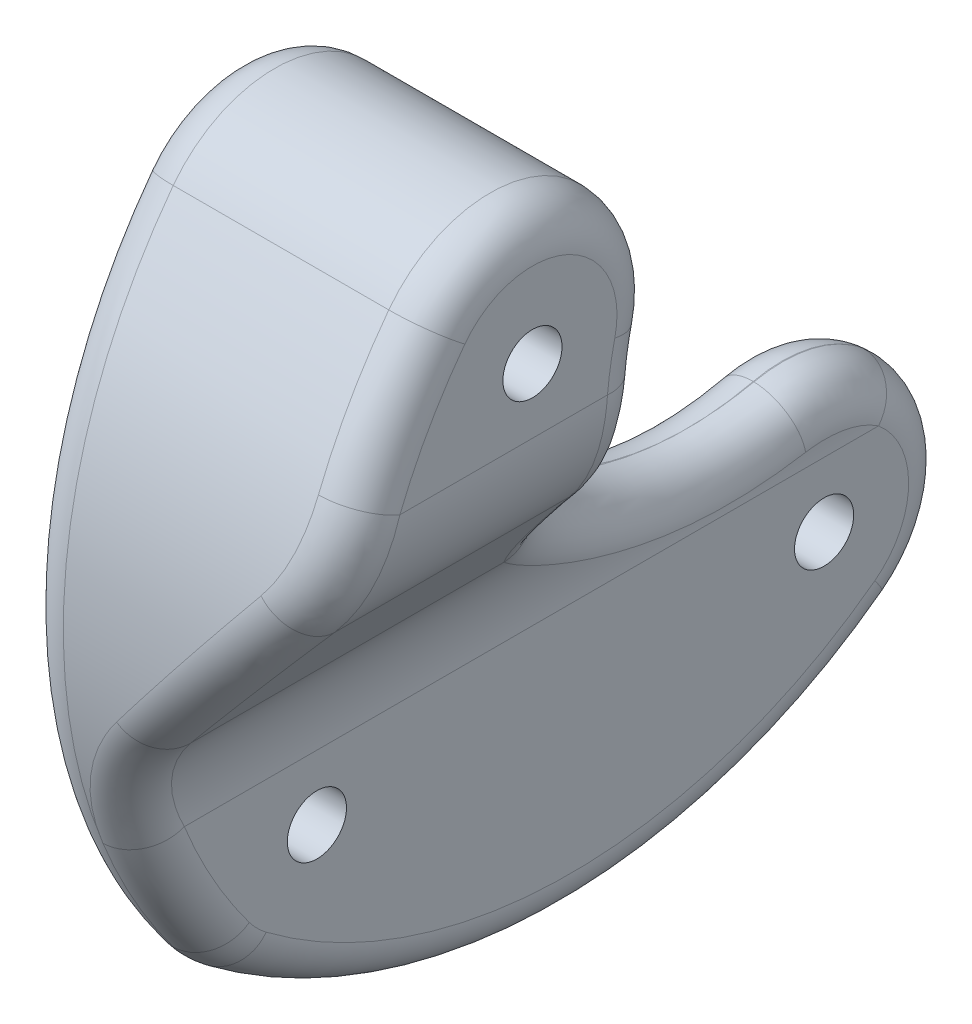
SolidWorks part; units mm, degrees
ref_plane "Alzado" through (0, 0, 0) normal (1, 0, 0) x (0, 1, 0)
ref_plane "Planta" through (0, 0, 0) normal (0, 0, 1) x (0, 1, 0)
ref_plane "Vista lateral" through (0, 0, 0) normal (0, 1, 0) x (-1, 0, 0)
sketch "Croquis2" plane through (0, 0, 0) normal (0, 0, 1) x (0, 1, 0)
  line L0 (-25, 0) -> (75, 0)
  line L1 (75, 0) -> (75, -35.5)
  line L2 (75, -35.5) -> (45, -35.5)
  line L5 (-25, -10) -> (-25, 0)
  line L6 (0, 0) -> (60, 0) construction
  line L7 (60, 0) -> (60, -35.5) construction
  line L8 (-25, -10) -> (15, -10)
  line L9 (15, -10) -> (45, -35.5)
  arc A0 (75, 0) -> (-25, 0) centre (25, -97.9796) ccw construction
  arc A1 (30, -22.75) -> (15, -10) centre (15, -25.1985) ccw construction
  arc A2 (30, -22.75) -> (45, -35.5) centre (45, -20.3015) ccw construction
  point P3 (-12.1025, -12.5808)
  point P5 (-30, -10)
  point P15 (15.2372, -35.5)
  point P17 (-1.0211, -21.882)
  point P18 (-13.496, -10)
  point P19 (-0.9848, -21.9129)
  point P20 (-1.3677, -21.5875)
  point P21 (0, 0)
  point P22 (-30, -10)
  point P23 (0, 0)
  point P24 (0, 0)
  point P25 (30, 4.9741)
  point P26 (-33.6749, -10)
  point P27 (2.4991, -15.8993)
  point P29 (-34.8773, 0)
  point P30 (0, 0)
  dimension "D6" = 110
  dimension "D1" = 10
  dimension "D7" = 60
  dimension "D3" = 15
  dimension "D4" = 25
  dimension "D2" = 15
  dimension "D5" = 25.5
extrude "Saliente-Extruir1" add sketch "Croquis2" along normal mid plane 120
sketch "Croquis5" plane through (0, 0, 0) normal (1, 0, 0) x (0, 1, 0)
  line L0 (75, 60) -> (75, -60) construction
  line L1 (0, 35) -> (30, 5) construction
  line L2 (75, 0) -> (-25, 0) construction
  line L3 (0, 35) -> (60, 35) construction
  line L5 (0, 35) -> (0, -25) construction
  line L6 (0, -25) -> (60, 35) construction
  line L10 (-25, 60) -> (15, 60) construction
  line L11 (75, 0) -> (-25, 0) construction
  line L12 (-25, 0) -> (-25, -60) construction
  arc A0 (-9, 47) -> (69, 47) centre (30, -5) cw
  arc A1 (-9, 47) -> (-12, 44) centre (0, 35) ccw
  arc A2 (56.6125, 20.3875) -> (69, 47) centre (60, 35) ccw
  arc A3 (-12, -34) -> (14.6125, -21.6125) centre (0, -25) ccw
  circle A6 centre (0, 35) radius 3
  circle A7 centre (60, 35) radius 3
  circle A8 centre (0, -25) radius 3
  arc A9 (-12, 44) -> (-12, -34) centre (40, 5) ccw
  arc A10 (56.6125, 20.3875) -> (14.6125, -21.6125) centre (48.7083, -13.7083) ccw
  point P20 (-25, 5)
  dimension "D4" = 45
  dimension "D5" = 6
  dimension "D3" = 25
  dimension "D6" = 15
  dimension "D7" = 35
  dimension "D1" = 90
  dimension "D2" = 60
extrude "Cortar-Extruir1" cut sketch "Croquis5" against normal through all both and the other way through all flip side to cut
ref_plane "Plano1" through (-20, 0, 0) normal (1, 0, 0) x (0, 1, 0)
sketch "Croquis8" plane through (-20, 0, 0) normal (1, 0, 0) x (0, 1, 0)
  point P0 (0, -25)
  point P2 (60, 35)
  point P4 (0, 35)
hole_wizard "Refrentado para tornillo con cabeza troncocónica de M61" positions "Croquis8" profile "Croquis10" counterbore size "M6" standard "Ansi Metric"
sketch "Croquis10" plane through (-20, 0, -25) normal (0, 1, 0) x (0, 0, 1)
  line L0 (0, 0) -> (0, 57.603)
  line L1 (0, 57.603) -> (3.5, 55.5)
  line L2 (3.5, 55.5) -> (3.5, 4.6)
  line L3 (3.5, 4.6) -> (6.5, 4.6)
  line L4 (6.5, 4.6) -> (6.5, 0)
  line L5 (6.5, 0) -> (0, 0)
  line L10 (0, 57.603) -> (-3.5, 55.5) construction
  line L11 (0, -6.35) -> (0, 107.95) construction
  dimension "Diámetro de taladro" = 7
  dimension "Profundidad de taladro" = 55.5
  dimension "Diámetro de refrentado" = 13
  dimension "Profundidad de refrentado" = 4.6
  dimension "Ángulo de perforador" = 118
fillet "Redondeo3" radius 20 2 edges at (35.5, 45, 39.6701) (10, 15, 26.979)
fillet "Redondeo4" radius 5 20 edges at (0, 23.9595, 11.0405) (0, 6.33, -38.5989) (0, -25, 5) (0, -10.6066, 45.6066) (0, 30, 60) (11.0525, 14.051, 58.0129) (10, -1.0067, 52.1278) (10, -10.6066, 45.6066) (10, -25, 5) (10, -2.9229, -39.7125) (10.9602, 13.7711, -30.9461) (11.0158, 13.9412, -9.6771) (21.8339, 28.9222, 15.1623) (34.5894, 46.3855, 21.2146) (35.5, 54.493, 20.8104) (35.5, 73.5989, 28.67) (35.5, 61.0067, 52.1278) (34.0976, 44.9943, 58.2469) (0, 73.5989, 28.67) (22.75, 30, 60)
equation "\"esp\"=10"
equation "\"D1@Croquis2\"=\"esp\""
